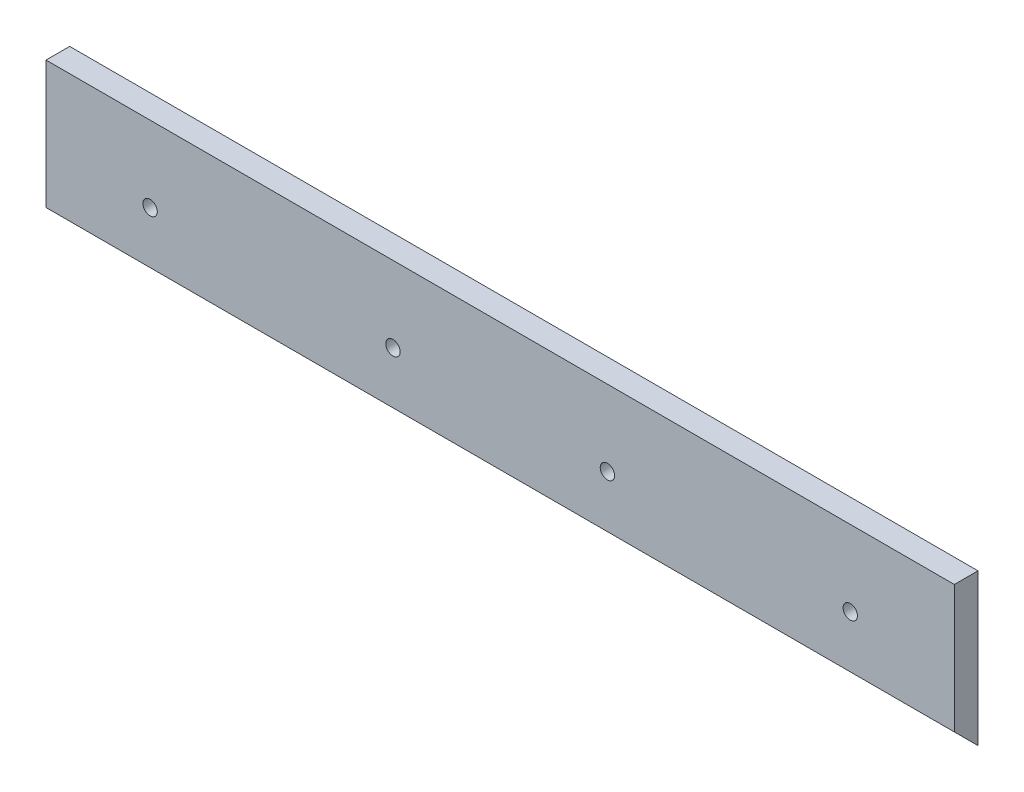
SolidWorks part; units mm, degrees
ref_plane "Front Plane" through (0, 0, 0) normal (0, 0, 1) x (1, 0, 0)
ref_plane "Top Plane" through (0, 0, 0) normal (0, 1, 0) x (1, 0, 0)
ref_plane "Right Plane" through (0, 0, 0) normal (1, 0, 0) x (0, 0, -1)
sketch "Sketch1" plane through (0, 0, 0) normal (0, 0, 1) x (1, 0, 0)
  line L1 (304.8, 50.8) -> (-304.8, 50.8)
  line L2 (304.8, 50.8) -> (304.8, -50.8)
  line L3 (304.8, -50.8) -> (-304.8, -50.8)
  line L4 (-304.8, 50.8) -> (-304.8, -50.8)
  line L5 (304.8, 50.8) -> (-304.8, -50.8) construction
  line L6 (304.8, -50.8) -> (-304.8, 50.8) construction
  point P0 (0, 0)
  dimension "D1" = 101.6
  dimension "D2" = 609.6
extrude "Boss-Extrude1" add sketch "Sketch1" along normal mid plane 15.875
sketch "Sketch2" plane through (304.8, 0, 0) normal (1, 0, 0) x (0, 0, -1)
  line L0 (-7.9375, 50.8) -> (7.9375, 34.925)
  line L1 (7.9375, -50.8) -> (7.9375, 50.8) construction
  line L2 (7.9375, 34.925) -> (7.9375, 50.8)
  line L3 (7.9375, 50.8) -> (-7.9375, 50.8)
  dimension "D1" = 45
extrude "Cut-Extrude1" [suppressed] cut sketch "Sketch2" against normal through all both and the other way through all
sketch "Sketch3" plane through (304.8, 0, 0) normal (1, 0, 0) x (0, 0, -1)
  line L0 (7.9375, -50.8) -> (-7.9375, -34.925)
  line L1 (-7.9375, -50.8) -> (-7.9375, 50.8) construction
  line L2 (-7.9375, -34.925) -> (-7.9375, -50.8)
  line L3 (-7.9375, -50.8) -> (7.9375, -50.8)
  dimension "D1" = 45
extrude "Cut-Extrude2" cut sketch "Sketch3" against normal through all both and the other way through all
sketch "Sketch4" plane through (0, 0, -7.9375) normal (0, 0, -1) x (-1, 0, 0)
  line L0 (0, 0) -> (0, 50.8) construction
  line L1 (-304.8, 50.8) -> (304.8, 50.8) construction
  line L2 (-304.8, -50.8) -> (-304.8, 50.8) construction
  circle A0 centre (-234.95, 0) radius 13.1826
  circle A1 centre (-234.95, 0) radius 4.826
  circle A2 centre (-71.9667, 0) radius 13.1826
  circle A3 centre (-71.9667, 0) radius 4.826
  circle A4 centre (71.9667, 0) radius 4.826
  circle A5 centre (234.95, 0) radius 4.826
  circle A6 centre (234.95, 0) radius 13.1826
  circle A7 centre (71.9667, 0) radius 13.1826
  dimension "D1" = 9.652
  dimension "D2" = 26.3652
  dimension "D4" = 143.9333
  dimension "D3" = 69.85
extrude "Cut-Extrude3" cut sketch "Sketch4" against normal through all both and the other way through all contours A1 | A3 | A4 | A5 region at (234.95, 0, -7.9375) region at (71.9667, 0, -7.9375) region at (-71.9667, 0, -7.9375) region at (-234.95, 0, -7.9375)
extrude "Cut-Extrude4" cut sketch "Sketch4<3>" against normal blind 8.128
sketch "Sketch4<3>" plane through (0, 0, -7.9375) normal (0, 0, -1) x (-1, 0, 0) same geometry as "Sketch4"
